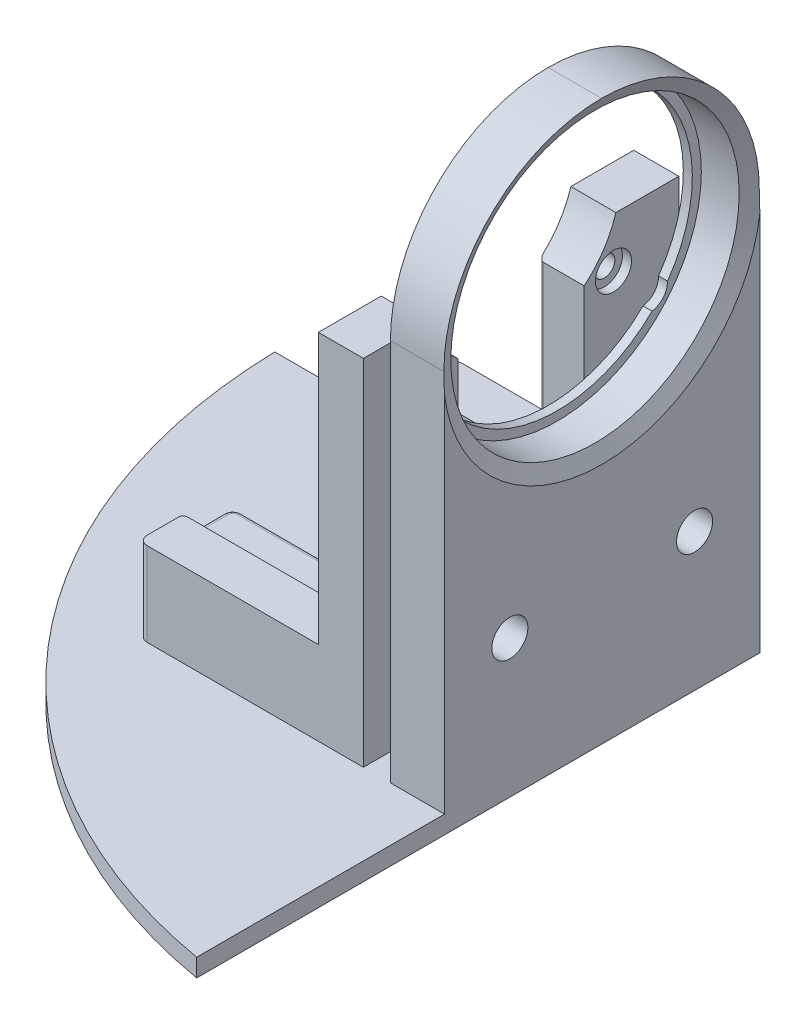
SolidWorks part; units mm, degrees
ref_plane "정면" through (0, 0, 0) normal (0, 0, 1) x (1, 0, 0)
ref_plane "윗면" through (0, 0, 0) normal (0, 1, 0) x (1, 0, 0)
ref_plane "우측면" through (0, 0, 0) normal (1, 0, 0) x (0, 0, -1)
sketch "스케치1" plane through (0, 0, 0) normal (0, 1, 0) x (1, 0, 0)
  line L1 (-11.1518, -1.5362) -> (-64.9818, -1.5362)
  line L2 (-11.1518, -1.5362) -> (-11.1518, -64.0362)
  arc A0 (-64.9818, -1.5362) -> (-11.1518, -64.0362) centre (0, 0) ccw
  point P1 (0, 0)
  dimension "D1" = 130
  dimension "D2" = 53.83
  dimension "D3" = 62.5
extrude "보스-돌출1" add sketch "스케치1" along normal blind 2 contours L1 A0 L2 region at (-33.5603, 0, 27.1054)
sketch "스케치2" plane through (0, 2, 0) normal (0, 1, 0) x (1, 0, 0)
  line L1 (-11.1518, -1.5362) -> (-17.1518, -1.5362)
  line L2 (-11.1518, -1.5362) -> (-11.1518, -36.5362)
  line L3 (-11.1518, -36.5362) -> (-17.1518, -36.5362)
  line L4 (-17.1518, -1.5362) -> (-17.1518, -36.5362)
  dimension "D1" = 35
  dimension "D2" = 6
extrude "보스-돌출2" add sketch "스케치2" along normal blind 60
fillet "필렛1" radius 17.5 2 edges at (-14.1518, 62, 1.5362) (-14.1518, 62, 36.5362)
sketch "스케치3" plane through (-11.1518, 0, 0) normal (1, 0, 0) x (0, 0, -1)
  circle A0 centre (-19.0362, 44.5) radius 16
  dimension "D1" = 32
extrude "컷-돌출1" cut sketch "스케치3" against normal blind 5
chamfer "모따기1" distance 0.8 angle 64 1 edges at (-11.1518, 44.5, 3.0362) first distance on face at (-16.1518, 44.5, 3.0362)
sketch "스케치4" plane through (-16.1518, 0, 0) normal (1, 0, 0) x (0, 0, -1)
  circle A0 centre (-19.0362, 44.5) radius 15
  circle A1 centre (-19.0362, 44.5) radius 16 construction
  dimension "D1" = 1
extrude "컷-돌출2" cut sketch "스케치4" against normal through all
sketch "스케치5" plane through (0, 2, 0) normal (0, 1, 0) x (1, 0, 0)
  line L0 (-17.1518, -1.5362) -> (-64.9818, -1.5362) construction
  line L1 (-20.1518, -1.5362) -> (-45.1518, -1.5362)
  line L2 (-20.1518, -1.5362) -> (-20.1518, -12.0362)
  line L3 (-20.1518, -12.0362) -> (-45.1518, -12.0362)
  line L4 (-45.1518, -1.5362) -> (-45.1518, -12.0362)
  line L5 (-17.1518, -1.5362) -> (-17.1518, -36.5362) construction
  line L6 (-20.1518, -26.0362) -> (-45.1518, -26.0362)
  line L7 (-20.1518, -26.0362) -> (-20.1518, -36.5362)
  line L8 (-20.1518, -36.5362) -> (-45.1518, -36.5362)
  line L9 (-45.1518, -26.0362) -> (-45.1518, -36.5362)
  dimension "D1" = 10.5
  dimension "D2" = 25
  dimension "D3" = 35
  dimension "D4" = 3
extrude "보스-돌출3" add sketch "스케치5" along normal blind 7.3
sketch "스케치6" plane through (0, 9.3, 0) normal (0, 1, 0) x (1, 0, 0)
  line L0 (-45.1518, -31.5362) -> (-25.1518, -31.5362)
  line L1 (-45.1518, -1.5362) -> (-20.1518, -1.5362)
  line L2 (-45.1518, -1.5362) -> (-45.1518, -6.5362)
  line L3 (-25.1518, -12.0362) -> (-20.1518, -12.0362)
  line L4 (-20.1518, -1.5362) -> (-20.1518, -12.0362)
  line L5 (-45.1518, -36.5362) -> (-20.1518, -36.5362)
  line L6 (-45.1518, -36.5362) -> (-45.1518, -31.5362)
  line L7 (-25.1518, -26.0362) -> (-20.1518, -26.0362)
  line L8 (-20.1518, -36.5362) -> (-20.1518, -26.0362)
  line L9 (-45.1518, -6.5362) -> (-25.1518, -6.5362)
  line L10 (-25.1518, -6.5362) -> (-25.1518, -12.0362)
  line L11 (-25.1518, -31.5362) -> (-25.1518, -26.0362)
  line L12 (-45.1518, -12.0362) -> (-20.1518, -12.0362) construction
  line L13 (-45.1518, -26.0362) -> (-20.1518, -26.0362) construction
  line L14 (-25.1518, -36.5362) -> (-25.1518, -26.0362) construction
  line L15 (-45.1518, -31.5362) -> (-20.1518, -31.5362) construction
  line L16 (-25.1518, -1.5362) -> (-25.1518, -12.0362) construction
  line L17 (-45.1518, -6.5362) -> (-20.1518, -6.5362) construction
  dimension "D1" = 5.5
  dimension "D2" = 5.5
  dimension "D3" = 5
  dimension "D4" = 5
extrude "보스-돌출4" add sketch "스케치6" along normal blind 2
fillet "필렛2" radius 1 4 edges at (-45.1518, 6.65, 36.5362) (-45.1518, 5.65, 26.0362) (-45.1518, 5.65, 12.0362) (-45.1518, 6.65, 1.5362)
sketch "스케치7" plane through (-25.1518, 0, 0) normal (-1, 0, 0) x (0, 0, 1)
  line L0 (12.0362, 9.3) -> (12.0362, 2) construction
  line L1 (1.5362, 11.3) -> (12.0362, 11.3)
  line L2 (1.5362, 11.3) -> (1.5362, 41.3)
  line L3 (1.5362, 41.3) -> (8.512, 41.3)
  line L4 (12.0362, 11.3) -> (12.0362, 36.0147)
  line L5 (36.5362, 11.3) -> (26.0362, 11.3)
  line L6 (36.5362, 11.3) -> (36.5362, 41.3)
  line L7 (36.5362, 41.3) -> (29.5605, 41.3)
  line L8 (26.0362, 11.3) -> (26.0362, 36.0147)
  arc A0 (26.0362, 36.0147) -> (29.5605, 41.3) centre (19.0362, 44.5) ccw
  arc A1 (8.512, 41.3) -> (12.0362, 36.0147) centre (19.0362, 44.5) ccw
  dimension "D2" = 22
  dimension "D1" = 30
extrude "보스-돌출5" add sketch "스케치7" against normal blind 5
sketch "스케치9" plane through (-25.1518, 0, 0) normal (-1, 0, 0) x (0, 0, 1)
  line L0 (6.5362, 9.3) -> (12.0362, 9.3) construction
  line L1 (8.7862, 35.8) -> (29.2862, 35.8) construction
  line L2 (8.7862, 35.8) -> (8.7862, 15.3) construction
  line L3 (8.7862, 15.3) -> (29.2862, 15.3) construction
  line L4 (29.2862, 35.8) -> (29.2862, 15.3) construction
  circle A0 centre (19.0362, 44.5) radius 15 construction
  circle A1 centre (8.7862, 35.8) radius 1.15
  circle A2 centre (8.7862, 15.3) radius 1.15
  circle A3 centre (29.2862, 15.3) radius 1.15
  circle A4 centre (29.2862, 35.8) radius 1.15
  dimension "D4" = 10.25
  dimension "D5" = 2.3
  dimension "D1" = 20.5
  dimension "D2" = 20.5
  dimension "D3" = 6
extrude "컷-돌출3" cut sketch "스케치9" against normal through all
sketch "스케치10" plane through (-11.1518, 0, 0) normal (1, 0, 0) x (0, 0, -1)
  circle A0 centre (-29.2862, 15.3) radius 2
  circle A1 centre (-8.7862, 15.3) radius 2
  circle A2 centre (-8.7862, 35.8) radius 2
  circle A3 centre (-29.2862, 35.8) radius 2
  dimension "D1" = 4
extrude "컷-돌출4" cut sketch "스케치10" against normal blind 10
fillet "필렛3" radius 0.5 12 edges at (-45.1518, 10.3, 6.5362) (-45.1518, 10.3, 31.5362) (-34.6518, 9.3, 12.0362) (-44.859, 9.3, 11.7433) (-34.6518, 9.3, 26.0362) (-44.859, 9.3, 26.3291) (-45.1518, 9.3, 8.7862) (-45.1518, 9.3, 29.2862) (-35.1518, 9.3, 31.5362) (-35.1518, 9.3, 6.5362) (-25.1518, 22.6574, 26.0362) (-25.1518, 22.6574, 12.0362)
